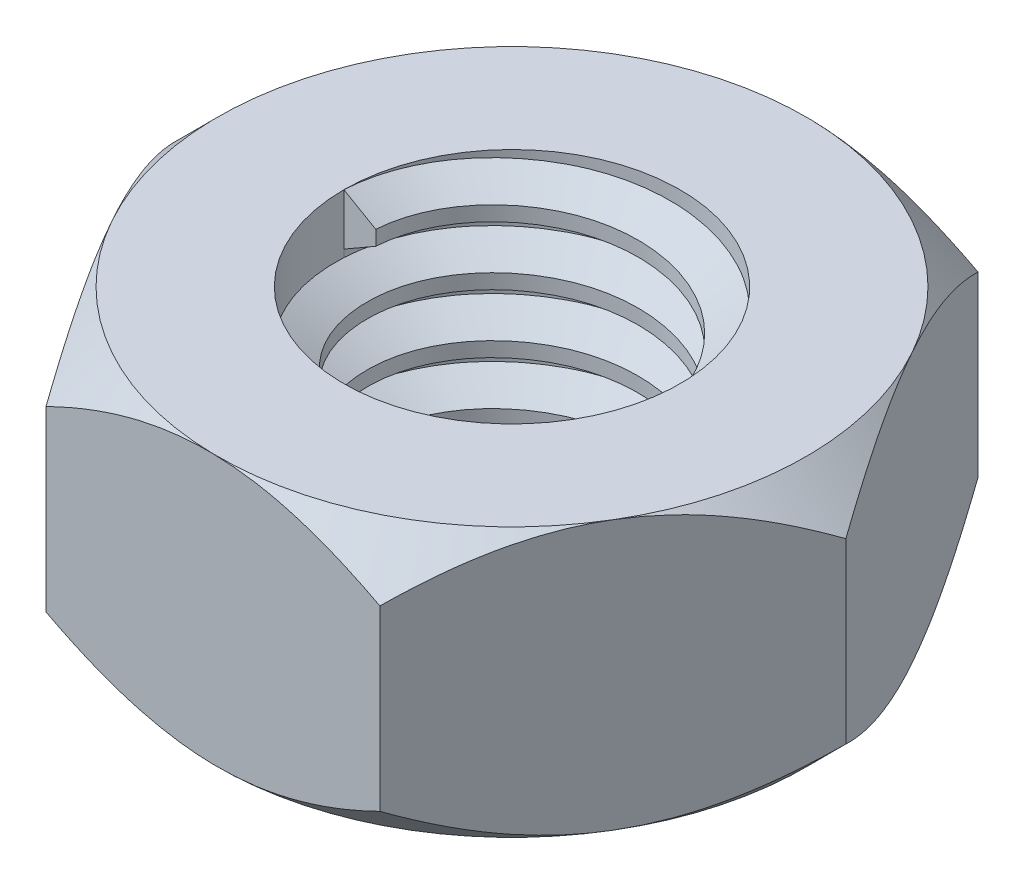
SolidWorks part; units mm, degrees
ref_plane "Front Plane" through (0, 0, 0) normal (0, 0, 1) x (1, 0, 0)
ref_plane "Top Plane" through (0, 0, 0) normal (0, 1, 0) x (1, 0, 0)
ref_plane "Right Plane" through (0, 0, 0) normal (1, 0, 0) x (0, 0, -1)
sketch "Sketch1" plane through (0, 0, 0) normal (0, 1, 0) x (1, 0, 0)
  line L1 (2.0793, 3.4655) -> (-1.9616, 3.5335)
  line L2 (-1.9616, 3.5335) -> (-4.0409, 0.068)
  line L3 (-4.0409, 0.068) -> (-2.0793, -3.4655)
  line L4 (-2.0793, -3.4655) -> (1.9616, -3.5335)
  line L5 (1.9616, -3.5335) -> (4.0409, -0.068)
  line L6 (4.0409, -0.068) -> (2.0793, 3.4655)
  circle A0 centre (0, 0) radius 3.5 construction
  circle A1 centre (0, 0) radius 2
  dimension "D2" = 4
  dimension "D1" = 7
  dimension "D3" = 1.9616
extrude "Boss-Extrude1" add sketch "Sketch1" along normal blind 3.2
sketch "Sketch2" plane through (0, 3.2, 0) normal (0, 1, 0) x (1, 0, 0)
  circle A0 centre (0, 0) radius 3.5
  dimension "D1" = 7
extrude "Cut-Extrude1" cut sketch "Sketch2" against normal blind 3.2 draft 45 flip side to cut
ref_plane "Plane1" through (0, 1.6, 0) normal (0, -1, 0) x (-1, 0, 0)
mirror "Mirror1" about plane through (0, 1.6, 0) normal (0, -1, 0) of "Cut-Extrude1"
thread "Thread1" pitch 0.7 method extrude profile "Thread Profile1" start angle 0, offset 0, length 2.5, pitch 0.7, diameter 4
ref_plane "Plane2" through (-2, 3.2, 0) normal (0, 0, 1) x (-1, 0, 0)
sketch "Thread Profile1" plane through (-2, 3.2, 0) normal (0, 0, 1) x (-1, 0, 0)
  line L0 (0, 0) -> (0, 0.7) construction
  line L11 (0, 0) -> (0, 0.6125)
  line L12 (0, 0.6125) -> (-0.3789, 0.3937)
  line L13 (-0.3789, 0.3937) -> (-0.3789, 0.2187)
  line L15 (-0.3789, 0.2187) -> (0, 0)
  line L17 (-0.3789, 0.3062) -> (0, 0.3062) construction
  point P2 (0, 0)
  dimension "Pitch" = 0.7
  dimension "Profile_Angle" = 60
  dimension "Profile_Land" = 0.175
  dimension "Profile_Height" = 0.3789
